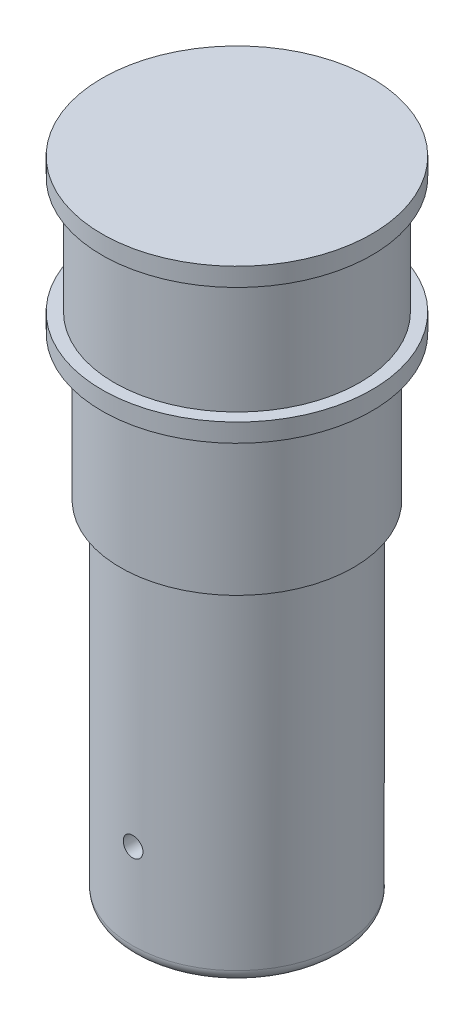
SolidWorks part; units mm, degrees
material "ABS"
ref_plane "Front Plane" through (0, 0, 0) normal (0, 0, 1) x (1, 0, 0)
ref_plane "Top Plane" through (0, 0, 0) normal (0, 1, 0) x (1, 0, 0)
ref_plane "Right Plane" through (0, 0, 0) normal (1, 0, 0) x (0, 0, -1)
sketch "Sketch1" plane through (0, 0, 0) normal (0, 0, 1) x (1, 0, 0)
  line L2 (-8.5, -40) -> (-8.5, -11.8)
  line L3 (-9.5, 0) -> (-11, 0)
  line L4 (-11, 0) -> (-11, 1.5)
  line L5 (-11, 1.5) -> (-10, 1.5)
  line L6 (-10, 1.5) -> (-10, 11)
  line L7 (-10, 11) -> (-11, 11)
  line L8 (-11, 11) -> (-11, 12.5)
  line L9 (-11, 12.5) -> (0, 12.5)
  line L10 (0, 12.5) -> (0, -26)
  line L11 (-4, -40) -> (-8.5, -40)
  line L12 (-4, -26) -> (-4, -40)
  line L13 (0, -26) -> (-4, -26)
  line L14 (-8.5, -11.8) -> (-9.5, -11.8)
  line L15 (-9.5, -11.8) -> (-9.5, 0)
  dimension "D1" = 8.5
  dimension "D2" = 1
  dimension "D3" = 40
  dimension "D4" = 1.5
  dimension "D5" = 4
  dimension "D6" = 14
  dimension "D7" = 12.5
  dimension "D8" = 10
  dimension "D9" = 28.2
  dimension "D10" = 1
revolve "Revolve1" add sketch "Sketch1" angle 360 about L10
fillet "Fillet1" radius 1 2 edges at (-8.5, -40, 0) (-4, -40, 0)
hole_wizard "M2x0.4 Tapped Hole1" positions "Sketch2" profile "Sketch3" tap size "M2x0.4" standard "ANSI Metric" end condition up to next
sketch "Sketch2" plane through (0, 0, 0) normal (0, 0, 1) x (1, 0, 0)
  line L0 (-7.5, -40) -> (7.5, -40) construction
  point P0 (0, -32)
  dimension "D1" = 8
sketch "Sketch3" plane through (0, -32, 0) normal (1, 0, 0) x (0, 1, 0)
  line L0 (0, 0) -> (0, 8.5)
  line L1 (0, 8.5) -> (0.8, 8.5)
  line L2 (0.8, 8.5) -> (0.8, 0)
  line L5 (0.8, 0) -> (0, 0)
  line L11 (0, -6.35) -> (0, 107.95) construction
  dimension "Thru Tap Drill Dia." = 1.6
  dimension "Thru Tap Drill Depth" = 8.5
cosmetic thread "Hole Thread1" parameters "D2"=2
